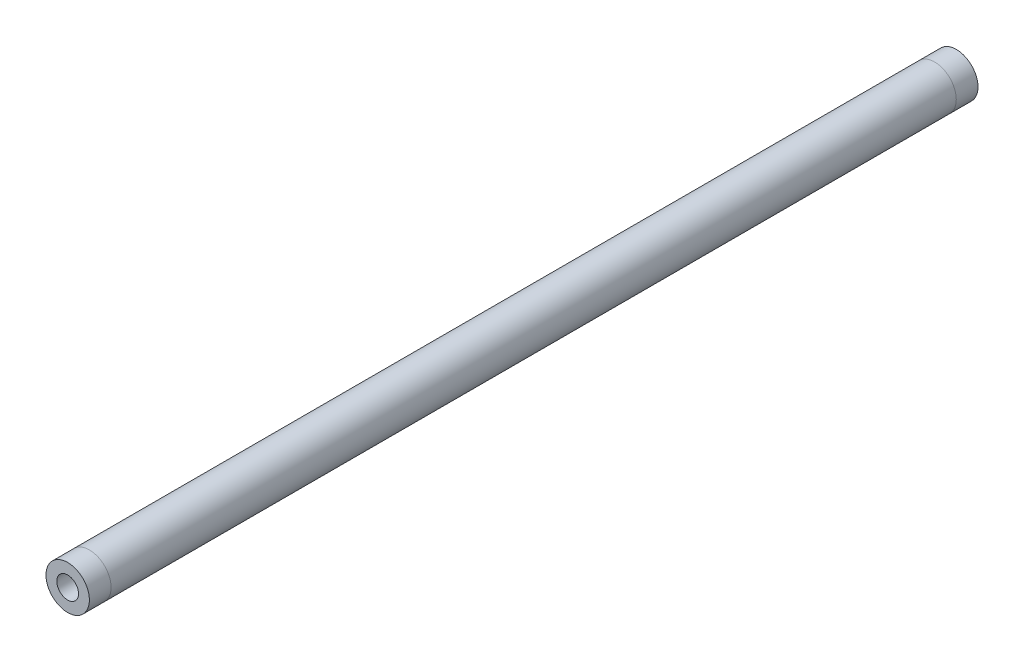
SolidWorks part; units mm, degrees
material "AISI 4130 Steel, annealed at 865C"
ref_plane "Front Plane" through (0, 0, 0) normal (0, 0, 1) x (1, 0, 0)
ref_plane "Top Plane" through (0, 0, 0) normal (0, 1, 0) x (1, 0, 0)
ref_plane "Right Plane" through (0, 0, 0) normal (1, 0, 0) x (0, 0, -1)
sketch "Axis" plane through (0, 0, 0) normal (1, 0, 0) x (0, 0, -1)
  line L0 (0, 0) -> (259.9107, 0) construction
  line L1 (259.9107, 0) -> (253.5607, 0)
  line L2 (259.9107, 0) -> (281.8055, 0) construction
  line L3 (0, 0) -> (-21.8948, 0) construction
  point P4 (0, 0)
  point P5 (259.9107, 0)
  point P6 (253.5607, 0)
  point P8 (281.8055, 0)
  dimension "D1" = 6.35
  dimension "D2" = 21.8948
  dimension "D3" = 21.8948
sketch "Sketch1" plane through (0, 0, 0) normal (0, 0, 1) x (1, 0, 0)
  circle A0 centre (0, 0) radius 6.35
  circle A1 centre (0, 0) radius 4.826
  circle A2 centre (0, 0) radius 3.175
  dimension "D1" = 12.7
  dimension "D2" = 1.524
  dimension "D3" = 6.35
extrude "Threaded insert 1-1" add sketch "Sketch1" against normal blind 6.35 contours A0 A1 | A1 A2 region at (-6.1704, 0, 0) region at (-4.6895, 0, 0)
extrude "Threaded insert 1-2" add sketch "Sketch1<3>" against normal blind 9.525 from surface contours A1 A2 region at (-4.6895, 0, 0) starting at face at (6.35, 0, -6.35)
sketch "Sketch1<3>" plane through (0, 0, 0) normal (0, 0, 1) x (1, 0, 0) same geometry as "Sketch1"
extrude "Tube extrude" add sketch "Sketch1<4>" against normal up to vertex (253.5607 mm away) from surface separate body contours A0 A1 region at (-6.1704, 0, 0) up to point (0, 0, -253.5607) starting at face at (4.826, 0, -6.35)
sketch "Sketch1<4>" plane through (0, 0, 0) normal (0, 0, 1) x (1, 0, 0) same geometry as "Sketch1"
extrude "Threaded insert 2-1" add sketch "Sketch1<6>" along normal blind 9.525 from surface separate body contours A1 A2 region at (-4.6895, 0, 0) starting at face at (4.826, 0, -253.5607)
sketch "Sketch1<6>" plane through (0, 0, 0) normal (0, 0, 1) x (1, 0, 0) same geometry as "Sketch1"
extrude "Threaded insert 2-2" add sketch "Sketch1<9>" against normal blind 6.35 from surface separate body contours A1 A2 | A0 A1 region at (-6.1704, 0, 0) region at (-4.6895, 0, 0) starting at face at (4.826, 0, -253.5607)
sketch "Sketch1<9>" plane through (0, 0, 0) normal (0, 0, 1) x (1, 0, 0) same geometry as "Sketch1"
combine bodies "Combine1" operation type add bodies to combine 106 104
equation "\"Threaded insert outer thickness\"= .25"
equation "\"D1@Threaded insert 1-1\"=\"Threaded insert outer thickness\""
equation "\"D1@Threaded insert 2-2\"=\"Threaded insert outer thickness\""
equation "\"D1@Axis\" = \"Threaded insert outer thickness\""
